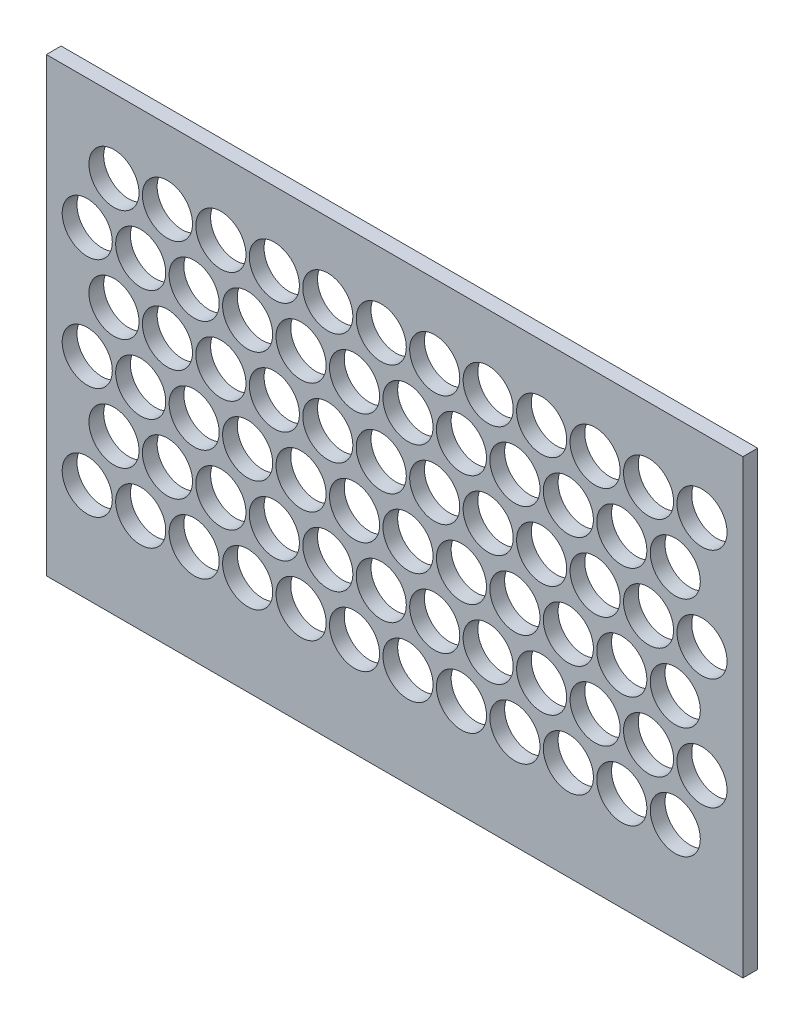
SolidWorks part; units mm, degrees
material "ABS"
ref_plane "X-Y Datum" through (0, 0, 0) normal (0, 0, 1) x (1, 0, 0)
ref_plane "X-Z Datum" through (0, 0, 0) normal (0, 1, 0) x (1, 0, 0)
ref_plane "Y-Z Datum" through (0, 0, 0) normal (1, 0, 0) x (0, 0, -1)
sketch "Sketch1" plane through (0, 0, 0) normal (0, 0, 1) x (1, 0, 0)
  line L1 (-143.025, 70.775) -> (143.025, 70.775)
  line L2 (-143.025, 70.775) -> (-143.025, -70.775)
  line L3 (-143.025, -70.775) -> (143.025, -70.775)
  line L4 (143.025, 70.775) -> (143.025, -70.775)
  line L5 (-143.025, 70.775) -> (143.025, -70.775) construction
  line L6 (-143.025, -70.775) -> (143.025, 70.775) construction
  line L13 (-149.85, -102.6) -> (149.85, -102.6)
  line L14 (-149.85, 91.65) -> (149.85, 91.65)
  line L15 (-149.85, 91.65) -> (-149.85, -102.6)
  line L16 (149.85, 91.65) -> (149.85, -102.6)
  line L17 (149.85, 70.775) -> (149.85, -70.775) construction
  line L18 (-143.025, 91.65) -> (143.025, 91.65) construction
  line L19 (-143.025, -102.6) -> (143.025, -102.6) construction
  line L20 (-149.85, 70.775) -> (-149.85, -70.775) construction
  line L21 (-132.25, -60) -> (-109.25, -60) construction
  circle A0 centre (-132.25, -60) radius 10.775
  circle A1 centre (-109.25, -60) radius 10.775 construction
  circle A2 centre (-120.75, -36) radius 10.775
  point P0 (0, 0)
  point P16 (-120.75, -60)
  dimension "D1" = 21.55
  dimension "D2" = 23
  dimension "D3" = 24
  dimension "D5" = 141.55
  dimension "D6" = 286.05
  dimension "D7" = 31.825
  dimension "D8" = 20.875
  dimension "D9" = 6.825
  dimension "D10" = 6.825
extrude "Boss-Extrude1" add sketch "Sketch1" along normal blind 6.35 contours A0 L3 L4 L1 L2 A2 | A2 | A0 | A0 L2 L3 | L1 L4 L3 L2 region at (2.4105, 0.9241, 0) region at (-140.6182, -68.3682, 0) region at (-132.25, -60, 0) region at (-146.2785, -5.475, 0) region at (-120.75, -36, 0)
sketch "Sketch3" plane through (0, 0, 6.35) normal (0, 0, 1) x (1, 0, 0)
  line L4 (143.025, 70.775) -> (-143.025, 70.775)
  line L5 (143.025, -70.775) -> (143.025, 70.775)
  line L6 (-143.025, -70.775) -> (143.025, -70.775)
  line L7 (-143.025, 70.775) -> (-143.025, -70.775)
  line L8 (143.025, 70.775) -> (-143.025, 70.775)
  line L9 (143.025, -70.775) -> (143.025, 70.775)
  line L10 (-143.025, -70.775) -> (143.025, -70.775)
  line L11 (-143.025, 70.775) -> (-143.025, -70.775)
  circle A1 centre (-120.75, -36) radius 10.775
  circle A2 centre (-120.75, -36) radius 10.775
  circle A3 centre (-132.25, -60) radius 10.775
  circle A4 centre (-132.25, -60) radius 10.775
  dimension "D1" = 0
  dimension "D2" = 0
  dimension "D3" = 0
extrude "Cut-Extrude1" cut sketch "Sketch3" against normal through all contours A4 region at (-132.25, -60, 6.35)
sketch "Sketch4" plane through (0, 0, 6.35) normal (0, 0, 1) x (1, 0, 0)
  line L4 (143.025, 70.775) -> (-143.025, 70.775)
  line L5 (143.025, -70.775) -> (143.025, 70.775)
  line L6 (-143.025, -70.775) -> (143.025, -70.775)
  line L7 (-143.025, 70.775) -> (-143.025, -70.775)
  line L8 (143.025, 70.775) -> (-143.025, 70.775)
  line L9 (143.025, -70.775) -> (143.025, 70.775)
  line L10 (-143.025, -70.775) -> (143.025, -70.775)
  line L11 (-143.025, 70.775) -> (-143.025, -70.775)
  circle A1 centre (-120.75, -36) radius 10.775
  circle A2 centre (-120.75, -36) radius 10.775
  circle A3 centre (-132.25, -60) radius 10.775
  circle A4 centre (-132.25, -60) radius 10.775
  dimension "D1" = 0
  dimension "D2" = 0
  dimension "D3" = 0
extrude "Cut-Extrude2" cut sketch "Sketch4" against normal through all contours A2 region at (-120.75, -36, 6.35)
pattern_linear "LPattern1" count 12 spacing 23 along (1, 0, 0) of "Cut-Extrude1", "Cut-Extrude2"
pattern_linear "LPattern2" count 3 spacing 48 along (0, 1, 0) of "LPattern1"
